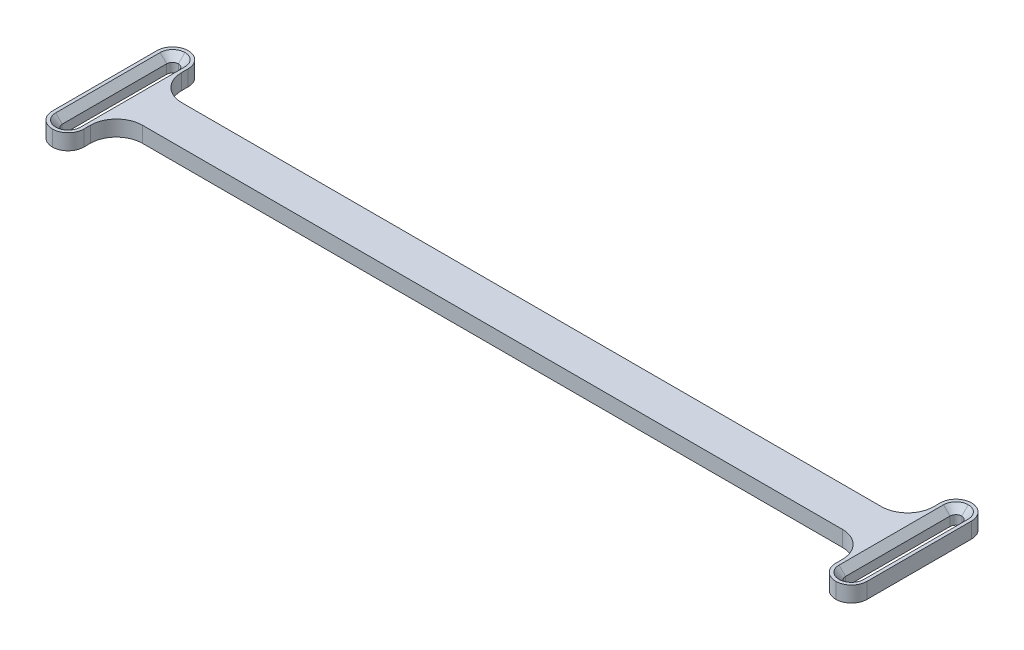
SolidWorks part; units mm, degrees
ref_plane "Front Plane" through (0, 0, 0) normal (0, 0, 1) x (1, 0, 0)
ref_plane "Top Plane" through (0, 0, 0) normal (0, 1, 0) x (1, 0, 0)
ref_plane "Right Plane" through (0, 0, 0) normal (1, 0, 0) x (0, 0, -1)
sketch "Sketch1" plane through (0, 0, 0) normal (0, 1, 0) x (1, 0, 0)
  line L0 (-152.25, 0) -> (-156, 0)
  line L1 (0, 0) -> (-85.6849, 0)
  line L2 (0, 0) -> (0, -7.5)
  line L3 (0, -7.5) -> (-144, -7.5)
  line L5 (-85.6849, 0) -> (-147.75, 0)
  line L6 (-144, -7.5) -> (-144, -26)
  line L7 (-144, -26) -> (-156, -26)
  line L8 (-156, 0) -> (-156, -26)
  line L10 (-147.75, 0) -> (-147.75, -22.25)
  line L11 (-147.75, -22.25) -> (-152.25, -22.25)
  line L12 (-152.25, 0) -> (-152.25, -22.25)
  dimension "D1" = 7.5
  dimension "D2" = 12
  dimension "D3" = 26
  dimension "D4" = 4.5
  dimension "D5" = 3.75
  dimension "D6" = 3.75
  dimension "D7" = 144
extrude "Boss-Extrude1" add sketch "Sketch1" along normal blind 6 contours L3 L6 L7 L8 L0 L12 L11 L10 L5 L1 L2
fillet "Fillet1" radius 10 1 edges at (-144, 3, 7.5)
fillet "Fillet2" radius 2.25 2 edges at (-152.25, 3, 22.25) (-147.75, 3, 22.25)
fillet "Fillet3" radius 6 2 edges at (-156, 3, 26) (-144, 3, 26)
chamfer "Chamfer1" distance 2.5 angle 45 4 edges at (-152.25, 6, 10) (-151.591, 6, 21.591) (-148.409, 6, 21.591) (-147.75, 6, 10)
mirror "Mirror1" about plane through (0, 6, 0) normal (0, 0, 1) of bodies 101
mirror "Mirror2" about plane through (0, 6, 0) normal (1, 0, 0) of bodies 102
equation "\"D5@Sketch1\"=0.5*(\"D2@Sketch1\"-\"D4@Sketch1\")"
equation "\"D6@Sketch1\"=\"D5@Sketch1\""
equation "\"D7@Sketch1\"=150 - (0.5*\"D4@Sketch1\"+\"D5@Sketch1\")"
